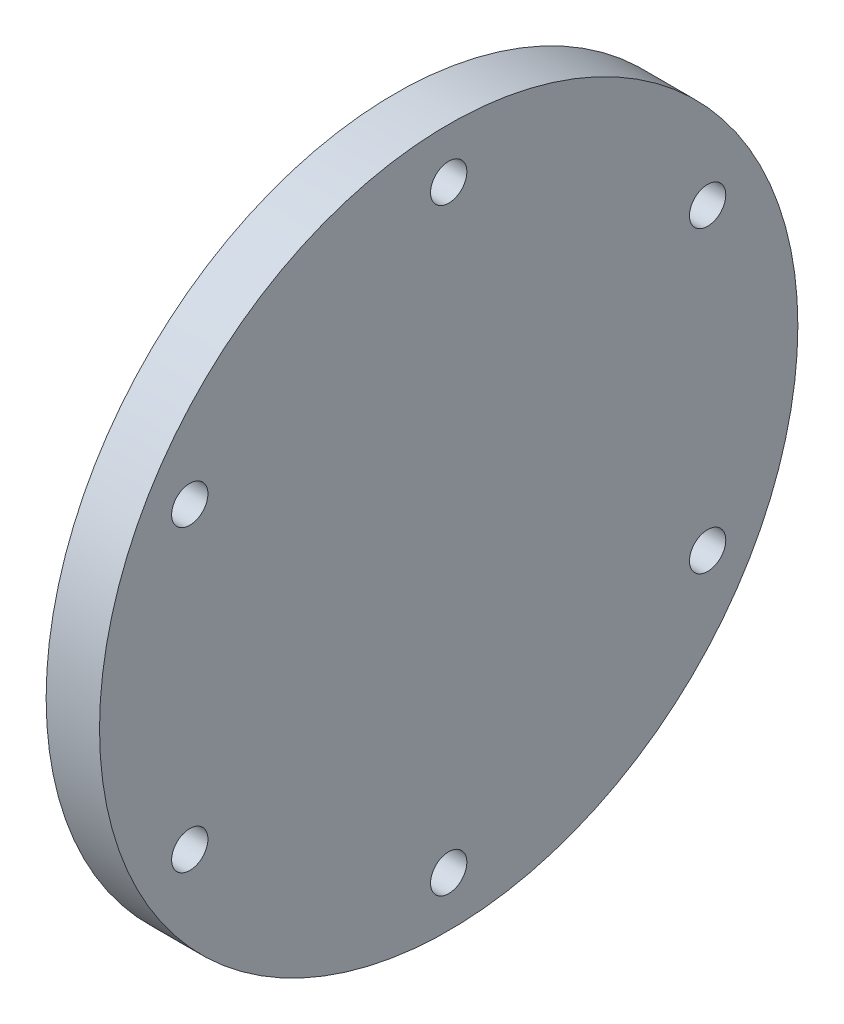
SolidWorks part; units mm, degrees
material "7075-O (SS)"
ref_plane "Front" through (0, 0, 0) normal (0, 0, 1) x (1, 0, 0)
ref_plane "Top" through (0, 0, 0) normal (0, 1, 0) x (1, 0, 0)
ref_plane "Right" through (0, 0, 0) normal (1, 0, 0) x (0, 0, -1)
sketch "Croquis1" plane through (0, 0, 0) normal (1, 0, 0) x (0, 0, -1)
  circle A0 centre (0, 0) radius 32.7
  dimension "D1" = 65.4
extrude "Saliente-Extruir1" add sketch "Croquis1" along normal blind 5
hole_wizard "Taladro de margen para M31" positions "Croquis2" profile "Croquis3" hole size "M3" standard "Ansi Metric"
sketch "Croquis2" plane through (5, 0, 0) normal (1, 0, 0) x (0, 0, -1)
  line L0 (0, 2.75) -> (0, -2.75) construction
  line L1 (2.75, 0) -> (-2.75, 0) construction
  point P0 (0, 28)
  point P12 (24.2487, 14)
  point P13 (24.2487, -14)
  point P14 (0, -28)
  point P15 (-24.2487, -14)
  point P16 (-24.2487, 14)
  point P18 (0, -26.8983)
  point P20 (0, 28)
  dimension "D1" = 28
  dimension "D3" = 28
  dimension "D2" = 6
sketch "Croquis3" plane through (5, 28, 0) normal (0, 1, 0) x (0, 0, -1)
  line L0 (0, 0) -> (0, 11.0215)
  line L1 (0, 11.0215) -> (1.7, 10)
  line L2 (1.7, 10) -> (1.7, 0)
  line L5 (1.7, 0) -> (0, 0)
  line L10 (0, 11.0215) -> (-1.7, 10) construction
  line L11 (0, -6.35) -> (0, 107.95) construction
  dimension "Diámetro de taladro" = 3.4
  dimension "Profundidad de taladro" = 10
  dimension "Ángulo de perforador" = 118
